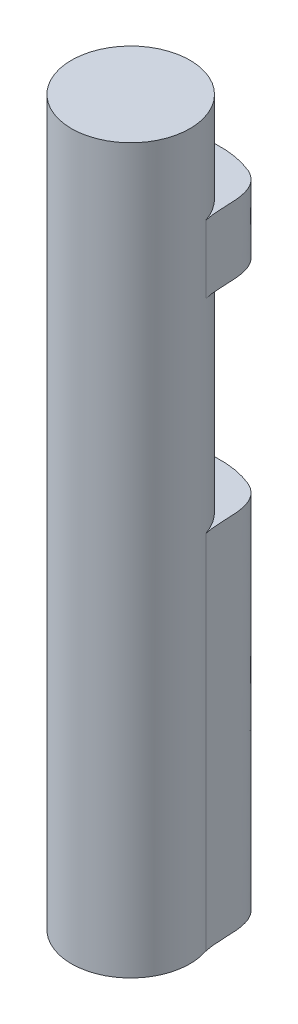
SolidWorks part; units mm, degrees
ref_plane "Front Plane" through (0, 0, 0) normal (0, 0, 1) x (1, 0, 0)
ref_plane "Top Plane" through (0, 0, 0) normal (0, 1, 0) x (1, 0, 0)
ref_plane "Right Plane" through (0, 0, 0) normal (1, 0, 0) x (0, 0, -1)
sketch "Sketch1" plane through (0, 0, 0) normal (0, 1, 0) x (1, 0, 0)
  circle A0 centre (0, 0) radius 25.273
  circle A1 centre (0, 0) radius 25.273
extrude "Boss-Extrude1" add sketch "Sketch1" along normal blind 203.2 contours A0
sketch "Sketch2" plane through (0, 203.2, 0) normal (0, 1, 0) x (1, 0, 0)
  circle A0 centre (0, 0) radius 16.6497
  circle A1 centre (0, 0) radius 25.273 construction
  spline S0 degree 3 poles (-16.1314, 4.1218) (-13.2336, 7.9922) (-17.8746, 25.2503) (1.5488, 26.2881) (6.0478, 24.5387) knots 0 0 0 0 0.459844 1 1 1 1
  spline S1 degree 3 poles (16.1314, 4.1218) (13.5509, 11.4427) (18.5011, 21.9118) (6.0478, 24.5387) knots 0 0 0 0 1 1 1 1
  circle M2 centre (0, 0) radius 25.273
extrude "Cut-Extrude1" cut sketch "Sketch2" against normal blind 203.2 contours S1 A0 S0 M2 region at (17.2224, 203.2, -2.1655)
ref_plane "Plane1" through (0, 177.8, 0) normal (0, 1, 0) x (1, 0, 0)
ref_plane "Plane2" through (0, 101.6, 0) normal (0, 1, 0) x (1, 0, 0)
sketch "Sketch3" plane through (0, 177.8, 0) normal (0, 1, 0) x (1, 0, 0)
  circle A0 centre (0, 0) radius 16.6497
extrude "Cut-Extrude5" cut sketch "Sketch3" along normal blind 50.8 flip side to cut contours A0
sketch "Sketch4" plane through (0, 101.6, 0) normal (0, 1, 0) x (1, 0, 0)
  circle A0 centre (0, 0) radius 16.6497
extrude "Cut-Extrude6" cut sketch "Sketch4" along normal blind 57.15 flip side to cut
